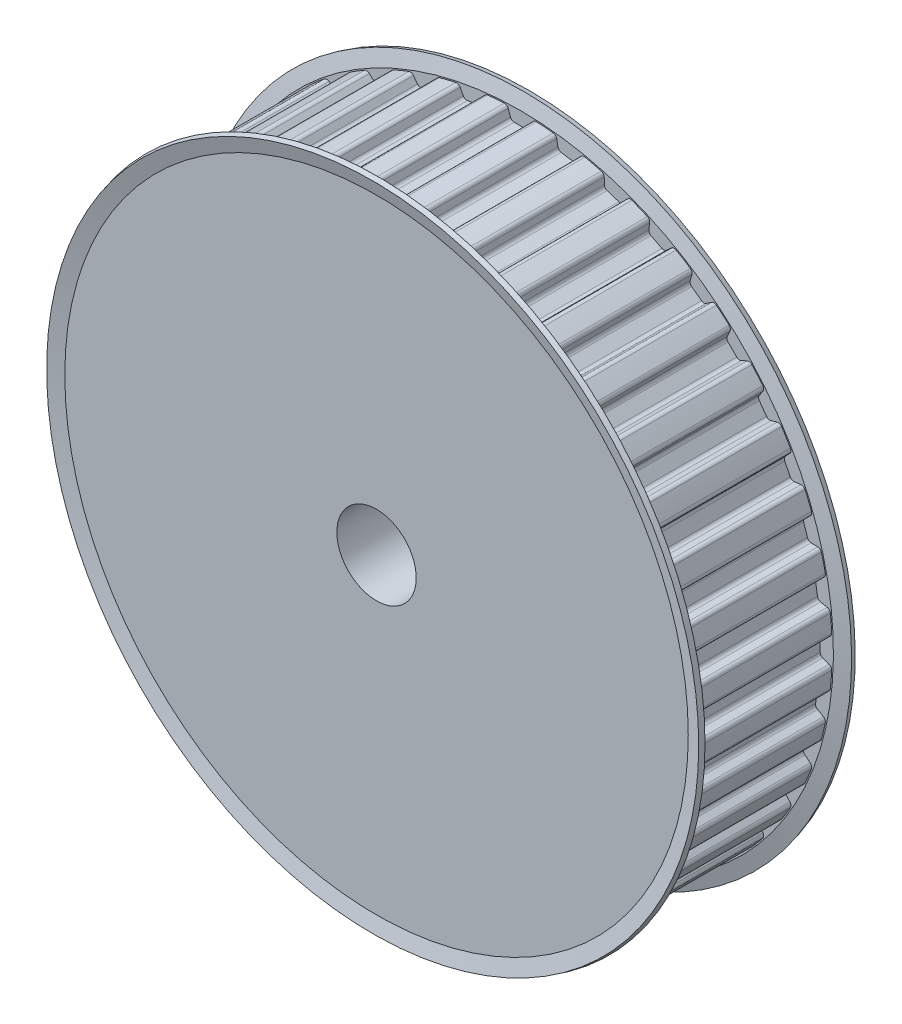
SolidWorks part; units mm, degrees
ref_plane "Front" through (0, 0, 0) normal (0, 0, 1) x (1, 0, 0)
ref_plane "Top" through (0, 0, 0) normal (0, 1, 0) x (1, 0, 0)
ref_plane "Right" through (0, 0, 0) normal (1, 0, 0) x (0, 0, -1)
sketch "support-front-body" plane through (0, 0, 0) normal (0, 0, 1) x (1, 0, 0)
  line L0 (0, 0) -> (0, 31.425) construction
  line L1 (0, 0) -> (0, -31.425) construction
  line L2 (0, 0) -> (31.425, 0) construction
  line L3 (0, 0) -> (-31.425, 0) construction
  circle A0 centre (0, 0) radius 31.425
  dimension "diam-outer" = 62.85
sketch "support-right-body" plane through (0, 0, 0) normal (1, 0, 0) x (0, 0, -1)
  line L0 (0, 0) -> (15, 0) construction
  line L1 (0, 31.425) -> (15, 31.425)
  line L2 (0, 31.425) -> (0, -31.425)
  line L3 (0, -31.425) -> (15, -31.425)
  line L4 (15, 31.425) -> (15, -31.425)
  dimension "width" = 15
sketch "support-right-hub" plane through (0, 0, 0) normal (1, 0, 0) x (0, 0, -1)
  line L0 (21, 0) -> (15, 0) construction
  line L1 (15, 20) -> (21, 20)
  line L2 (15, 20) -> (15, -20)
  line L3 (15, -20) -> (21, -20)
  line L4 (21, 20) -> (21, -20)
  line L5 (15, 31.425) -> (15, -31.425) construction
  line L6 (0, 0) -> (15, 0) construction
  line L8 (0, 31.425) -> (0, -31.425) construction
  dimension "diam-hub" = 40
  dimension "dist-hub" = 21
sketch "support-right-bore" plane through (0, 0, 0) normal (1, 0, 0) x (0, 0, -1)
  line L0 (0, 31.425) -> (0, -31.425) construction
  line L1 (0, 4) -> (21, 4)
  line L2 (0, 4) -> (0, -4)
  line L3 (0, -4) -> (21, -4)
  line L4 (21, 20) -> (21, -20) construction
  line L5 (21, 0) -> (0, 0) construction
  line L6 (0, 0) -> (15, 0) construction
  line L7 (21, 4) -> (21, -4)
  line L8 (21, -4) -> (21, 4) construction
  dimension "diam-bore" = 8
sketch "support-stop-screw-hole" plane through (0, 0, 0) normal (1, 0, 0) x (0, 0, -1)
  line L1 (6.5667, 11) -> (9.4333, 11)
  line L2 (6.5667, 11) -> (6.5667, -1)
  line L3 (8, -1) -> (9.4333, -1)
  line L4 (9.4333, 11) -> (9.4333, -1)
  line L5 (8, -1) -> (8, 11) construction
  line L6 (8, -1) -> (6.5667, -1)
  line L7 (0, 0) -> (8, 0) construction
  line L8 (0, 31.425) -> (0, -31.425) construction
  dimension "diam-stop-screw-hole" = 2.8665
  dimension "dist-stop-screw-hole" = 8
  dimension "depth-stop-screw-hole" = 12
  dimension "angle-stop-screw-hole" = 180
  dimension "height-stop-screw-hole" = 11
sketch "support-front-keygroove" plane through (0, 0, 0) normal (0, 0, 1) x (1, 0, 0)
  line L0 (0, 0) -> (0, -4) construction
  line L1 (-1, 4) -> (1, 4)
  line L2 (-1, 4) -> (-1, 1.8)
  line L3 (-1, 1.8) -> (1, 1.8)
  line L4 (1, 4) -> (1, 1.8)
  line L5 (0, 0) -> (0, 4) construction
  circle A0 centre (0, 0) radius 4 construction
  dimension "width-keygroove" = 2
  dimension "dist-keygroove" = 8
  dimension "height-keygroove" = 2.2
sketch "support-front-tooth" plane through (0, 0, 0) normal (0, 0, 1) x (1, 0, 0)
  line L0 (0, 0) -> (0, 32.5831) construction
  line L1 (-1.2259, 31.1204) -> (-0.9958, 30.4882)
  line L2 (-1.6224, 32.5831) -> (1.6224, 32.5831)
  line L3 (1.6224, 32.5831) -> (1.6224, 31.3831)
  line L4 (-1.6224, 32.5831) -> (-1.6224, 31.3831)
  line L5 (-2.5, 32.5831) -> (2.5, 32.5831) construction
  line L6 (1.6224, 31.3831) -> (2.5, 32.5831) construction
  line L7 (0, 31.425) -> (0, 30.225) construction
  line L8 (0, 31.425) -> (1.6224, 31.425) construction
  line L10 (-0.6199, 30.225) -> (0.6199, 30.225)
  line L11 (1.2259, 31.1204) -> (0.9958, 30.4882)
  line L12 (-0.9958, 30.4882) -> (-0.9, 30.225) construction
  line L13 (-0.9, 30.225) -> (-0.6199, 30.225) construction
  line L14 (0.9958, 30.4882) -> (0.9, 30.225) construction
  line L15 (0.9, 30.225) -> (0.6199, 30.225) construction
  circle A0 centre (0, 0) radius 31.425 construction
  arc A1 (-0.9958, 30.4882) -> (-0.6199, 30.225) centre (-0.6199, 30.625) ccw
  arc A3 (1.6224, 31.3831) -> (1.2259, 31.1204) centre (1.6018, 30.9836) ccw
  circle A4 centre (0, 0) radius 31.425 construction
  arc A5 (-1.6224, 31.3831) -> (-1.2259, 31.1204) centre (-1.6018, 30.9836) cw
  arc A6 (0.9958, 30.4882) -> (0.6199, 30.225) centre (0.6199, 30.625) cw
  point P26 (0, 30.225)
  dimension "rad-top" = 0.4
  dimension "rad-bottom" = 0.4
  dimension "height-tooth" = 1.2
  dimension "pitch" = 5
  dimension "angle" = 40
  dimension "width-tooth-bottom" = 1.8
sketch "support-right-flange" plane through (0, 0, 0) normal (1, 0, 0) x (0, 0, -1)
  line L0 (0, 28.7137) -> (0, 31.425)
  line L1 (15, 31.425) -> (15, -31.425) construction
  line L2 (0, 31.425) -> (0.5, 31.425) construction
  line L3 (0.5, 31.559) -> (0.1139, 33)
  line L4 (-0.3861, 32.866) -> (0.1139, 33)
  line L5 (0.5, 31.559) -> (0.5, 28.7137)
  line L6 (0.5, 28.7137) -> (0, 28.7137)
  line L7 (7.5, 31.425) -> (7.5, 0) construction
  line L8 (0, 31.425) -> (15, 31.425) construction
  line L9 (0, 31.425) -> (-0.3861, 32.866)
  line L10 (14.5, 28.7137) -> (15, 28.7138)
  line L11 (14.5, 31.559) -> (14.5, 28.7137)
  line L12 (15.3861, 32.866) -> (14.8861, 33)
  line L13 (14.5, 31.559) -> (14.8861, 33)
  line L14 (15, 31.425) -> (15.3861, 32.866)
  line L15 (15, 28.7138) -> (15, 31.425)
  line L16 (15, 0) -> (0, 0) construction
  line L17 (15, -28.7138) -> (15, -31.425)
  line L18 (15, -31.425) -> (15.3861, -32.866)
  line L19 (14.5, -31.559) -> (14.8861, -33)
  line L20 (15.3861, -32.866) -> (14.8861, -33)
  line L21 (14.5, -31.559) -> (14.5, -28.7138)
  line L22 (14.5, -28.7138) -> (15, -28.7138)
  line L23 (0.5, -28.7138) -> (0, -28.7138)
  line L24 (0.5, -31.559) -> (0.5, -28.7138)
  line L25 (-0.3861, -32.866) -> (0.1139, -33)
  line L26 (0.5, -31.559) -> (0.1139, -33)
  line L27 (0, -31.425) -> (-0.3861, -32.866)
  line L28 (0, -28.7138) -> (0, -31.425)
  line L29 (0, 0) -> (15, 0) construction
  line L30 (0, 31.425) -> (0.5, 31.559) construction
  line L31 (0.25, 28.7137) -> (0.25, 30.0694) construction
  line L32 (0.25, 30.0694) -> (0.25, 31.425) construction
  line L33 (-0.1361, 32.933) -> (0.25, 31.492) construction
  line L34 (0, 31.425) -> (15, 31.425) construction
  line L35 (0, 31.425) -> (0, -31.425) construction
  dimension "angle-flange" = 15
  dimension "thickness-flange" = 0.5
  dimension "diam-flange-inner" = 57.4275
  dimension "diam-flange-outer" = 66
  dimension "diam-flange-angle" = 62.85
ref_axis "ref-axis-center" through (0, 0, -15) along (0, 0, 1)
ref_plane "ref-plane-front" through (0, 0, 0) normal (0, 0, 1) x (1, 0, 0)
ref_plane "ref-plane-back" through (0, 0, -15) normal (0, 0, 1) x (1, 0, 0)
ref_plane "ref-plane-hub-front" through (0, 0, -15) normal (0, 0, 1) x (1, 0, 0)
ref_plane "ref-plane-hub-back" through (0, 0, -21) normal (0, 0, 1) x (1, 0, 0)
ref_plane "ref-plane-bore-front" through (0, 0, 0) normal (0, 0, 1) x (1, 0, 0)
ref_plane "ref-plane-bore-back" through (0, 0, -21) normal (0, 0, 1) x (1, 0, 0)
ref_plane "ref-plane-stop-screw-hole-top" through (0, 11, 0) normal (0, 1, 0) x (-1, 0, 0)
ref_axis "ref-axis-stop-screw-hole" through (0, 11, -8) along (0, -1, 0)
sketch "Sketch5" plane through (0, 0, 0) normal (1, 0, 0) x (0, 0, -1)
  line L0 (15, 31.425) -> (15, -31.425) construction
  line L1 (0, 31.425) -> (15, 31.425) construction
  line L2 (0, 31.425) -> (0, -31.425) construction
  line L3 (0, 0) -> (15, 0) construction
  line L4 (15, 31.425) -> (15, 0)
  line L5 (0, 31.425) -> (15, 31.425)
  line L6 (0, 31.425) -> (0, 0)
  line L7 (0, 0) -> (15, 0) construction
  line L8 (0, 0) -> (15, 0)
revolve "body" add sketch "Sketch5" angle 360 about L7
sketch "Sketch16" plane through (0, 0, 0) normal (1, 0, 0) x (0, 0, -1)
  line L0 (21, 20) -> (21, -20) construction
  line L1 (15, 20) -> (21, 20) construction
  line L2 (21, 0) -> (15, 0) construction
  line L3 (15, 20) -> (15, -20) construction
  line L4 (21, 20) -> (21, 0)
  line L5 (15, 20) -> (21, 20)
  line L6 (21, 0) -> (15, 0) construction
  line L7 (15, 20) -> (15, 0)
  line L8 (21, 0) -> (15, 0)
revolve "body-hub" add sketch "Sketch16" angle 360 about L6
sketch "Sketch17" plane through (0, 0, 0) normal (1, 0, 0) x (0, 0, -1)
  line L1 (21, 0) -> (0, 0) construction
  line L2 (0, 4) -> (21, 4) construction
  line L3 (0, 4) -> (0, -4) construction
  line L4 (21, 4) -> (21, -4) construction
  line L5 (21, 0) -> (0, 0) construction
  line L6 (0, 4) -> (21, 4)
  line L7 (0, 4) -> (0, 0)
  line L8 (21, 0) -> (0, 0)
  line L9 (21, 4) -> (21, 0)
revolve "body-bore" cut sketch "Sketch17" angle 360 about L5
sketch "Sketch19" plane through (0, 0, 0) normal (1, 0, 0) x (0, 0, -1)
  line L0 (6.5667, 11) -> (9.4333, 11) construction
  line L1 (8, -1) -> (8, 11) construction
  line L2 (9.4333, 11) -> (9.4333, -1) construction
  line L3 (8, -1) -> (9.4333, -1) construction
  line L4 (8, 11) -> (9.4333, 11)
  line L5 (8, -1) -> (8, 11) construction
  line L6 (9.4333, 11) -> (9.4333, -1)
  line L7 (8, -1) -> (9.4333, -1)
  line L8 (8, -1) -> (8, 11)
revolve "body-stop-screw-hole" [suppressed] cut sketch "Sketch19" angle 360 about L5
pattern_circular "pattern-stop-screw-hole" [suppressed] count 2 every 90 about axis through (0, 0, -15) along (0, 0, 1)
sketch "Sketch21" plane through (0, 0, 0) normal (0, 0, 1) x (1, 0, 0)
  line L0 (-1, 4) -> (1, 4) construction
  line L1 (-1, 4) -> (-1, 1.8) construction
  line L2 (-1, 1.8) -> (1, 1.8) construction
  line L3 (1, 4) -> (1, 1.8) construction
  line L4 (-1, 4) -> (1, 4)
  line L5 (-1, 4) -> (-1, 1.8)
  line L6 (-1, 1.8) -> (1, 1.8)
  line L7 (1, 4) -> (1, 1.8)
extrude "cut-keygroove" [suppressed] cut sketch "Sketch21" against normal up to surface (17.5 mm away)
sketch "Sketch23" plane through (0, 0, 0) normal (0, 0, 1) x (1, 0, 0)
  line L6 (1.6224, 32.5831) -> (-1.6224, 32.5831)
  line L7 (1.6224, 31.3831) -> (1.6224, 32.5831)
  line L8 (0.9958, 30.4882) -> (1.2259, 31.1204)
  line L9 (-0.6199, 30.225) -> (0.6199, 30.225)
  line L10 (-1.2259, 31.1204) -> (-0.9958, 30.4882)
  line L11 (-1.6224, 32.5831) -> (-1.6224, 31.3831)
  line L12 (1.6224, 32.5831) -> (-1.6224, 32.5831)
  line L13 (1.6224, 31.3831) -> (1.6224, 32.5831)
  line L14 (0.9958, 30.4882) -> (1.2259, 31.1204)
  line L15 (-0.6199, 30.225) -> (0.6199, 30.225)
  line L16 (-1.2259, 31.1204) -> (-0.9958, 30.4882)
  line L17 (-1.6224, 32.5831) -> (-1.6224, 31.3831)
  arc A4 (1.6224, 31.3831) -> (1.2259, 31.1204) centre (1.6018, 30.9836) ccw
  arc A5 (0.6199, 30.225) -> (0.9958, 30.4882) centre (0.6199, 30.625) ccw
  arc A6 (-0.9958, 30.4882) -> (-0.6199, 30.225) centre (-0.6199, 30.625) ccw
  arc A7 (-1.2259, 31.1204) -> (-1.6224, 31.3831) centre (-1.6018, 30.9836) ccw
  arc A8 (1.6224, 31.3831) -> (1.2259, 31.1204) centre (1.6018, 30.9836) ccw
  arc A9 (0.6199, 30.225) -> (0.9958, 30.4882) centre (0.6199, 30.625) ccw
  arc A10 (-0.9958, 30.4882) -> (-0.6199, 30.225) centre (-0.6199, 30.625) ccw
  arc A11 (-1.2259, 31.1204) -> (-1.6224, 31.3831) centre (-1.6018, 30.9836) ccw
  dimension "D1" = 0
extrude "cut-tooth" cut sketch "Sketch23" against normal up to surface (15 mm away) up to plane "ref-plane-back"
pattern_circular "pattern-tooth" count 40 over 360 about axis through (0, 0, -15) along (0, 0, 1) of "cut-tooth"
sketch "Sketch25" plane through (0, 0, 0) normal (1, 0, 0) x (0, 0, -1)
  line L0 (0, 0) -> (15, 0) construction
  line L1 (0.5, 28.7137) -> (0, 28.7137) construction
  line L2 (0.5, 31.559) -> (0.5, 28.7137) construction
  line L4 (-0.3861, 32.866) -> (0.1139, 33) construction
  line L5 (0, 31.425) -> (-0.3861, 32.866) construction
  line L6 (0, 28.7137) -> (0, 31.425) construction
  line L7 (0, 0) -> (15, 0) construction
  line L8 (0.5, 28.7137) -> (0, 28.7137)
  line L9 (0.5, 31.559) -> (0.5, 28.7137)
  line L10 (-0.3861, 32.866) -> (0.1139, 33)
  line L11 (0.5, 31.559) -> (0.1139, 33) construction
  line L12 (0, 31.425) -> (-0.3861, 32.866)
  line L13 (0, 28.7137) -> (0, 31.425)
  line L14 (0.5, 31.559) -> (0.1139, 33)
revolve "body-flange-front" add sketch "Sketch25" angle 360 about L7
sketch "Sketch26" plane through (0, 0, 0) normal (1, 0, 0) x (0, 0, -1)
  line L0 (15, 0) -> (0, 0) construction
  line L1 (14.5, 28.7137) -> (15, 28.7138) construction
  line L2 (14.5, 31.559) -> (14.5, 28.7137) construction
  line L4 (15.3861, 32.866) -> (14.8861, 33) construction
  line L5 (15, 31.425) -> (15.3861, 32.866) construction
  line L6 (15, 28.7138) -> (15, 31.425) construction
  line L7 (15, 0) -> (0, 0) construction
  line L8 (14.5, 28.7137) -> (15, 28.7138)
  line L9 (14.5, 31.559) -> (14.5, 28.7137)
  line L10 (15.3861, 32.866) -> (14.8861, 33)
  line L11 (14.5, 31.559) -> (14.8861, 33) construction
  line L12 (15, 31.425) -> (15.3861, 32.866)
  line L13 (15, 28.7138) -> (15, 31.425)
  line L14 (14.5, 31.559) -> (14.8861, 33)
revolve "body-flange-back" add sketch "Sketch26" angle 360 about L7
sketch "Эскиз1" plane through (0, 0, 0) normal (0, 0, 1) x (1, 0, 0)
  circle A0 centre (0, 0) radius 3
  dimension "D1" = 6
extrude "Вырез-Вытянуть1" [suppressed] cut sketch "Эскиз1" against normal through all
equation "\"diam-flange-angle@support-right-flange\" = \"diam-outer@support-front-body\""
equation "\"diam-flange-inner@support-right-flange\"=(\"diam-outer@support-front-body\" - 2 * \"height-tooth@support-front-tooth\" )  * 0.95"
